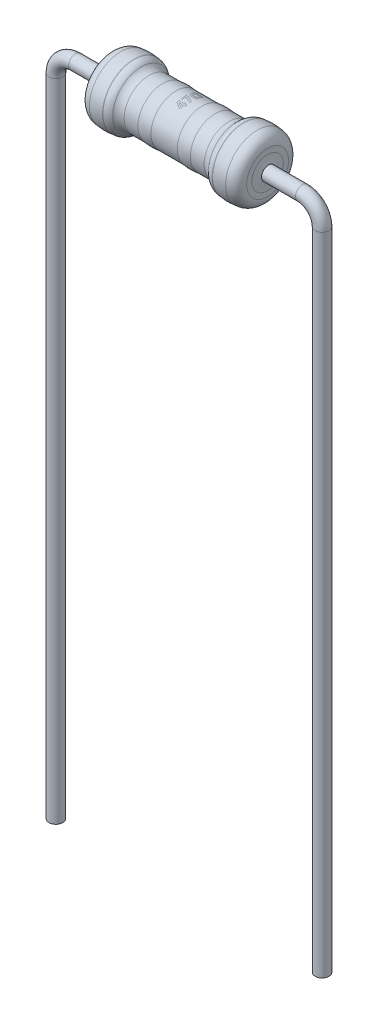
SolidWorks part; units mm, degrees
material "Plain Carbon Steel"
ref_plane "Front Plane" through (0, 0, 0) normal (0, 0, 1) x (1, 0, 0)
ref_plane "Top Plane" through (0, 0, 0) normal (0, 1, 0) x (1, 0, 0)
ref_plane "Right Plane" through (0, 0, 0) normal (1, 0, 0) x (0, 0, -1)
sketch "Sketch1" plane through (0, 0, 0) normal (0, 0, 1) x (1, 0, 0)
  line L0 (-4.33, 0) -> (4.33, 0)
  line L1 (-5.08, -0.75) -> (-5.08, -25.4)
  line L2 (5.08, -0.75) -> (5.08, -25.4)
  line L3 (-5.08, -25.4) -> (5.08, -25.4) construction
  line L4 (0, 0) -> (0, -25.4) construction
  arc A0 (-4.33, 0) -> (-5.08, -0.75) centre (-4.33, -0.75) ccw
  arc A1 (4.33, 0) -> (5.08, -0.75) centre (4.33, -0.75) cw
  dimension "D2" = 0.75
  dimension "D1" = 10.16
  dimension "D3" = 25.4
ref_plane "Plane1" through (-5.08, -25.4, 0) normal (0, -1, 0) x (-1, 0, 0)
sketch "Sketch2" plane through (-5.08, -25.4, 0) normal (0, -1, 0) x (-1, 0, 0)
  circle A0 centre (0, 0) radius 0.265
  dimension "D1" = 0.53
sweep "Sweep1" add profiles "Sketch2" path "Sketch1"
sketch "Sketch3" plane through (0, 0, 0) normal (0, 0, 1) x (1, 0, 0)
  line L0 (-3, 0) -> (3, 0)
  line L5 (-3, 0) -> (-3, 1.2)
  line L6 (3, 0) -> (3, 1.2)
  line L7 (-3, 1.2) -> (-1.75, 1.2)
  line L8 (3, 1.2) -> (1.75, 1.2)
  line L9 (-1.75, 1.2) -> (-1.75, 0.95)
  line L10 (-1.75, 0.95) -> (1.75, 0.95)
  line L11 (1.75, 0.95) -> (1.75, 1.2)
  line L12 (0, 0) -> (0, 0.95) construction
  dimension "D1" = 6
  dimension "D2" = 1.2
  dimension "D3" = 3.5
  dimension "D4" = 0.95
  dimension "D5" = 0.25
revolve "Revolve1" add sketch "Sketch3" angle 360 about L0
fillet "Fillet-1" radius 0.35 2 edges at (1.75, 0, 1.2) (-1.75, 0, 1.2)
fillet "Fillet-2" radius 0.4 4 edges at (3, 0, 1.2) (-3, 0, 1.2) (1.75, 0, 0.95) (-1.75, 0, 0.95)
sketch "Sketch5" plane through (0, 0, 0) normal (0, 0, 1) x (1, 0, 0)
  line L16 (-3, 0) -> (3, 0) construction
  line L17 (-2.6, 1.2) -> (-2.1, 1.2) construction
  line L18 (-2.6, 1.2) -> (-2.6, 0)
  line L19 (-2.6, 0) -> (-2.1, 0)
  line L20 (-2.1, 1.2) -> (-2.1, 0)
  line L21 (-1.75, 0.95) -> (1.75, 0.95) construction
  line L22 (2.6, 1.2) -> (2.1, 1.2) construction
  line L23 (2.6, 1.2) -> (2.6, 0)
  line L24 (2.6, 0) -> (2.1, 0)
  line L25 (2.1, 1.2) -> (2.1, 0)
  line L26 (-0.5, 0.95) -> (-1, 0.95) construction
  line L27 (-0.5, 0.95) -> (-0.5, 0)
  line L28 (-0.5, 0) -> (-1, 0)
  line L29 (-1, 0.95) -> (-1, 0)
  line L30 (-2.35, 1.2) -> (-2.35, 1.22) construction
  line L31 (1, 0.95) -> (0.5, 0.95) construction
  line L32 (1, 0.95) -> (1, 0)
  line L33 (1, 0) -> (0.5, 0)
  line L34 (0.5, 0.95) -> (0.5, 0)
  line L35 (-0.75, 0.95) -> (-0.75, 0.97) construction
  line L36 (0.75, 0.95) -> (0.75, 0.97) construction
  line L37 (2.35, 1.2) -> (2.35, 1.22) construction
  line L48 (-3, 0) -> (-3, 0.6)
  line L49 (-3, 0) -> (-3, 1.2) construction
  line L50 (-3, 0) -> (-3.05, 0)
  line L51 (-3.05, 0) -> (-3.05, 0.2)
  line L52 (3, 0) -> (3.05, 0)
  line L53 (3.05, 0) -> (3.05, 0.2)
  line L54 (3, 0) -> (3, 0.6)
  line L55 (3, 0) -> (3, 1.2) construction
  arc A0 (-2.6, 1.2) -> (-2.1, 1.2) centre (-2.35, -0.3525) cw
  arc A1 (-1, 0.95) -> (-0.5, 0.95) centre (-0.75, -0.6025) cw
  arc A2 (0.5, 0.95) -> (1, 0.95) centre (0.75, -0.6025) cw
  arc A3 (2.1, 1.2) -> (2.6, 1.2) centre (2.35, -0.3525) cw
  arc A6 (-3, 0.6) -> (-3.05, 0.2) centre (-4.625, 0.6) cw
  arc A7 (3.05, 0.2) -> (3, 0.6) centre (4.625, 0.6) cw
  dimension "D4" = 0.02
  dimension "D5" = 0.05
  dimension "D7" = 0.6
  dimension "D1" = 0.5
  dimension "D2" = 0.5
  dimension "D3" = 0.5
  dimension "D6" = 0.2
revolve "Revolve3" add sketch "Sketch5" angle 360 about L19
ref_plane "Plane2" through (0, 2, 0) normal (0, 1, 0) x (1, 0, 0)
sketch "Sketch6" plane through (0, 2, 0) normal (0, 1, 0) x (1, 0, 0)
  line L0 (0, 0) -> (0.15, 0) construction
  line L1 (0.15, 0.95) -> (0.15, -0.95) construction
  line L2 (0.5, 0.95) -> (-0.5, 0.95) construction
  text T0 "47Ω" font "Calibri" height 0.3
  dimension "D1" = 0.15
wrap "Wrap1" sketch "Sketch6" wrap type scribe source sketch "Sketch6" face at (-0.5, -0.95, 0)
